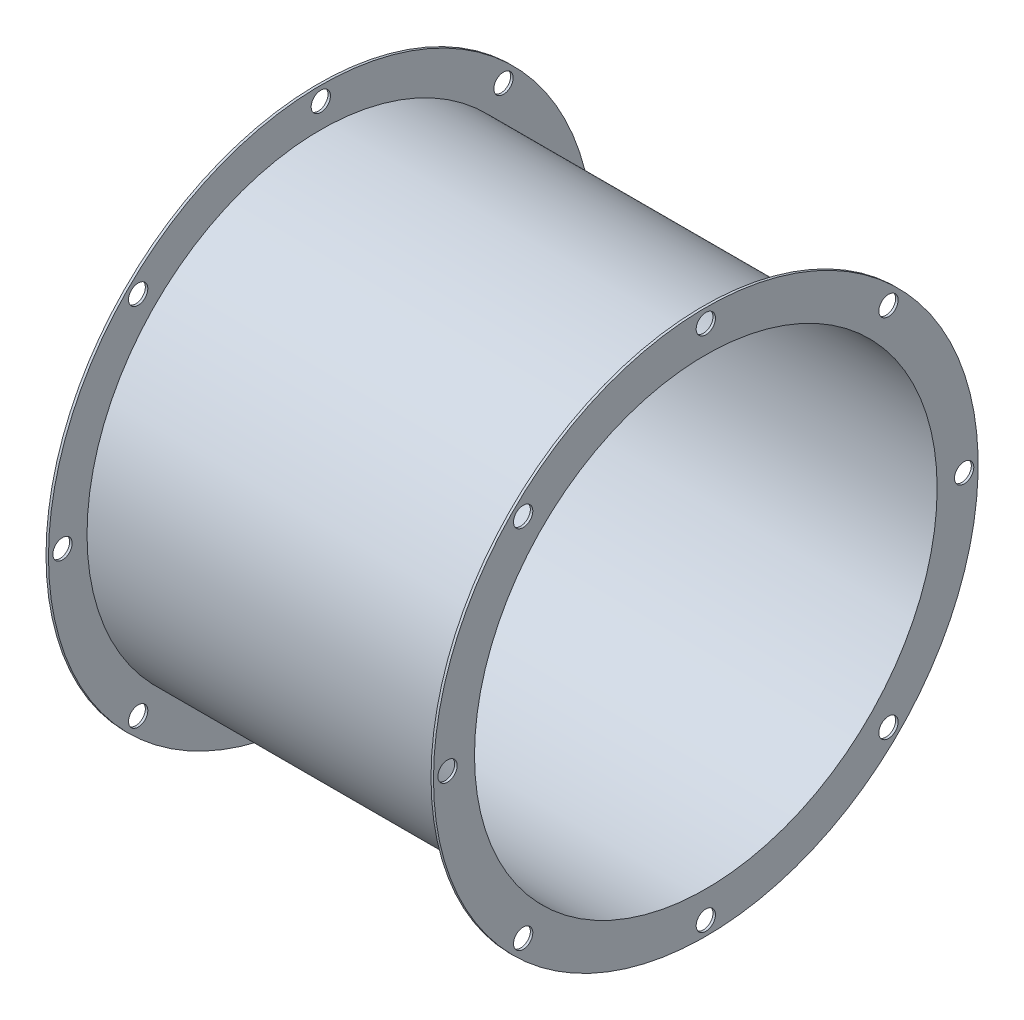
SolidWorks part; units mm, degrees
ref_plane "Front Plane" through (0, 0, 0) normal (0, 0, 1) x (1, 0, 0)
ref_plane "Top Plane" through (0, 0, 0) normal (0, 1, 0) x (1, 0, 0)
ref_plane "Right Plane" through (0, 0, 0) normal (1, 0, 0) x (0, 0, -1)
sketch "Sketch1" plane through (0, 0, 0) normal (0, 0, 1) x (1, 0, 0)
  line L0 (0, 0) -> (43.9716, 0) construction
  line L1 (0, 76.2) -> (127.635, 76.2)
  line L2 (127.635, 76.2) -> (127.635, 89.7128)
  line L3 (127.635, 89.7128) -> (126.8222, 89.7128)
  line L4 (126.8222, 89.7128) -> (126.8222, 77.0128)
  line L5 (126.8222, 77.0128) -> (0.8128, 77.0128)
  line L6 (0.8128, 77.0128) -> (0.8128, 89.7128)
  line L7 (0.8128, 89.7128) -> (0, 89.7128)
  line L8 (0, 89.7128) -> (0, 76.2)
  dimension "D1" = 0.8128
  dimension "D2" = 0.8128
  dimension "D3" = 0.8128
  dimension "D4" = 127.635
  dimension "D5" = 12.7
  dimension "D6" = 12.7
  dimension "D7" = 152.4
revolve "Revolve1" add sketch "Sketch1" angle 360 about L0
sketch "Sketch2" plane through (0, 0, 0) normal (1, 0, 0) x (0, 0, -1)
  circle A0 centre (0, 85.09) radius 3.175
  dimension "D2" = 6.35
  dimension "D1" = 85.09
extrude "Cut-Extrude1" cut sketch "Sketch2" along normal blind 224.79
pattern_circular "CirPattern1" count 8 over 360 about axis through (0, 0, 0) along (-1, 0, 0) of "Cut-Extrude1" reverse direction yes
